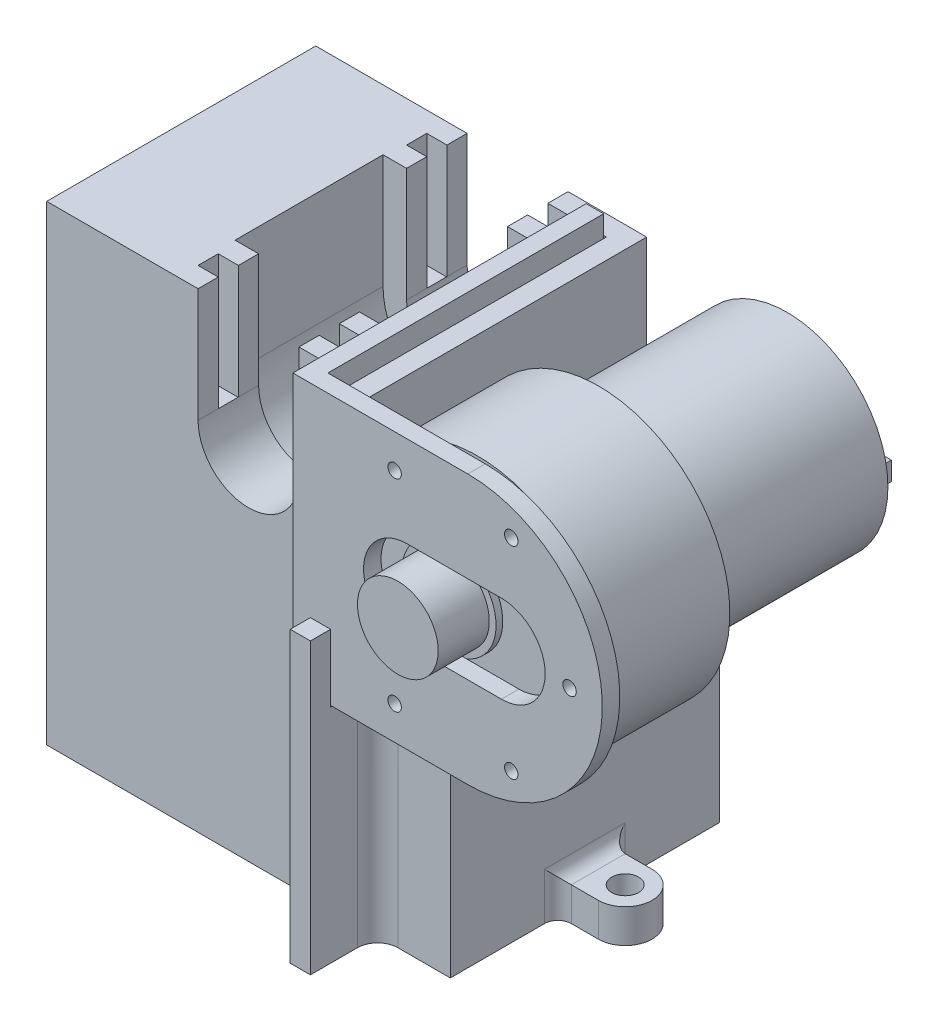
SolidWorks part; units mm, degrees
ref_plane "前视基准面" through (0, 0, 0) normal (0, 0, 1) x (1, 0, 0)
ref_plane "上视基准面" through (0, 0, 0) normal (0, 1, 0) x (1, 0, 0)
ref_plane "右视基准面" through (0, 0, 0) normal (1, 0, 0) x (0, 0, -1)
sketch "Sketch1" plane through (0, 5, 0) normal (0, 1, 0) x (1, 0, 0)
  line L1 (-150, -20) -> (-90, -20)
  line L2 (-150, -20) -> (-150, 20)
  line L3 (-150, 20) -> (-90, 20)
  line L4 (-90, -20) -> (-90, 20)
  line L5 (-150, -20) -> (-90, 20) construction
  line L6 (-150, 20) -> (-90, -20) construction
  point P0 (-120, 0)
  dimension "D1" = 40
  dimension "D2" = 60
  dimension "D3" = 120
extrude "Extrude1" add sketch "Sketch1" along normal blind 70
sketch "Sketch2" plane through (0, 0, 20) normal (0, 0, 1) x (1, 0, 0)
  circle A0 centre (-120, 58.05) radius 7.5
  circle A1 centre (-120, 58.05) radius 7.5
  point P5 (-120, 58.05)
sketch "Sketch4" plane through (0, 0, 20) normal (0, 0, 1) x (1, 0, 0)
  line L0 (-106.8, 75) -> (-106.8, 38)
  line L1 (-150, 75) -> (-90, 75) construction
  line L2 (-106.8, 38) -> (-69.3408, 38)
  line L3 (-69.3408, 38) -> (-69.3408, 101.6783)
  line L4 (-69.3408, 101.6783) -> (-106.8, 101.6783)
  line L5 (-106.8, 101.6783) -> (-106.8, 75)
  circle A0 centre (-88.8, 58.05) radius 3 construction
  point P5 (-120, 58.05)
  dimension "D1" = 31.2
  dimension "D2" = 6
  dimension "D3" = 18
  dimension "D4" = 37
extrude "Extrude2" cut sketch "Sketch4" against normal through all
sketch "Sketch5" plane through (0, 0, 20) normal (0, 0, 1) x (1, 0, 0)
  circle A0 centre (-120, 58.05) radius 7.5
  dimension "D1" = 15
extrude "Extrude3" cut sketch "Sketch5" against normal through all
sketch "Sketch7" plane through (0, 0, 20) normal (0, 0, 1) x (1, 0, 0)
  circle A0 centre (-120, 58.05) radius 11
  dimension "D1" = 22
ref_plane "Plane1" through (0, 0, 0) normal (0, 0, 1) x (1, 0, 0)
sketch "Sketch8" plane through (0, 0, 0) normal (0, 0, 1) x (1, 0, 0)
  circle A0 centre (-120, 58.05) radius 11 construction
  circle A1 centre (-120, 58.05) radius 11
extrude "Extrude5" cut sketch "Sketch8" against normal mid plane 22
sketch "Sketch9" plane through (0, 0, 20) normal (0, 0, 1) x (1, 0, 0)
  line L0 (-112.5, 75) -> (-112.5, 58.05)
  line L1 (-150, 75) -> (-106.8, 75) construction
  line L2 (-112.5, 58.05) -> (-127.5, 58.05)
  line L3 (-127.5, 58.05) -> (-127.5, 75)
  line L4 (-127.5, 75) -> (-112.5, 75)
  circle A3 centre (-120, 58.05) radius 7.5 construction
extrude "Extrude6" cut sketch "Sketch9" against normal through all
sketch "Sketch10" plane through (0, 0, 0) normal (0, 0, 1) x (1, 0, 0)
  line L0 (-109, 58.05) -> (-109, 89.3948)
  line L1 (-131, 58.05) -> (-131, 89.3948)
  line L2 (-131, 89.3948) -> (-109, 89.3948)
  line L3 (-131, 58.05) -> (-109, 58.05)
  circle A0 centre (-120, 58.05) radius 11 construction
  arc A1 (-109, 58.05) -> (-131, 58.05) centre (-120, 58.05) ccw construction
extrude "Extrude7" cut sketch "Sketch10" against normal mid plane 22
ref_plane "Plane2" through (0, 0, 27) normal (0, 0, 1) x (1, 0, 0)
ref_plane "Plane3" through (0, 0, -17) normal (0, 0, 1) x (1, 0, 0)
ref_plane "Plane4" through (0, 58, 0) normal (0, 1, 0) x (1, 0, 0)
sketch "Sketch13" plane through (-127.5, 0, 0) normal (1, 0, 0) x (0, 0, -1)
  line L0 (-20, 75) -> (20, 75) construction
  line L1 (-17, 75) -> (-14, 75)
  line L2 (-17, 75) -> (-17, 58)
  line L3 (-17, 58) -> (-14, 58)
  line L4 (-14, 75) -> (-14, 58)
  line L5 (3.135, 58) -> (-3.135, 58) construction
  line L6 (-11, 75) -> (-11, 58.05) construction
  dimension "D1" = 3
  dimension "D2" = 3
extrude "Extrude9" cut sketch "Sketch13" against normal blind 3
sketch "Sketch14" plane through (-112.5, 0, 0) normal (-1, 0, 0) x (0, 0, 1)
  line L0 (17, 75) -> (17, 58) construction
  line L1 (14, 58) -> (14, 75) construction
  line L2 (17, 58) -> (14, 58) construction
  line L3 (14, 75) -> (17, 75) construction
  line L4 (17, 75) -> (17, 58)
  line L5 (14, 58) -> (14, 75)
  line L6 (17, 58) -> (14, 58)
  line L7 (14, 75) -> (17, 75)
extrude "Extrude10" cut sketch "Sketch14" against normal blind 3
mirror "Mirror1" about plane through (0, 0, 0) normal (0, 0, 1) of "Extrude10", "Extrude9"
sketch "Sketch15" plane through (0, 0, 20) normal (0, 0, 1) x (1, 0, 0)
  line L0 (-112.5, 58.05) -> (-112.5, 75) construction
  line L1 (-127.5, 75) -> (-127.5, 58.05) construction
  line L2 (-112.5, 58.05) -> (-112.5, 75)
  line L3 (-127.5, 75) -> (-127.5, 58.05)
  line L4 (-127.5, 75) -> (-112.5, 75)
  circle A0 centre (-120, 58.05) radius 7.5 construction
  arc A1 (-112.5, 58.05) -> (-127.5, 58.05) centre (-120, 58.05) ccw
sketch "Sketch16" plane through (0, 0, -17) normal (0, 0, 1) x (1, 0, 0)
  line L0 (-106.8, 38) -> (-90, 38) construction
  line L1 (-100.8, 38) -> (-103.8, 38)
  line L2 (-100.8, 38) -> (-100.8, 75)
  line L3 (-100.8, 75) -> (-103.8, 75)
  line L4 (-103.8, 38) -> (-103.8, 75)
  line L5 (-106.8, 75) -> (-106.8, 38) construction
  line L6 (-127.5, 75) -> (-150, 75) construction
  dimension "D1" = 3
  dimension "D2" = 3
extrude "Extrude11" add sketch "Sketch16" along normal offset from surface (41 mm away) 3 up to plane "Plane2"
sketch "Sketch17" plane through (-100.8, 0, 0) normal (1, 0, 0) x (0, 0, -1)
  line L0 (17, 38) -> (17, 75) construction
  line L1 (17, 75) -> (20, 75)
  line L2 (17, 75) -> (17, 38)
  line L3 (17, 38) -> (20, 38)
  line L4 (20, 75) -> (20, 38)
  line L5 (-24, 75) -> (17, 75) construction
  line L6 (-20, 38) -> (17, 38) construction
  line L7 (20, 75) -> (20, 38) construction
extrude "Extrude12" add sketch "Sketch17" against normal up to surface (6 mm away) up to face at (-106.8, 56.5, 0)
sketch "Sketch18" plane through (0, 38, 0) normal (0, -1, 0) x (1, 0, 0)
  line L0 (-150, 20) -> (-90, 20) construction
  line L1 (-100.8, 20) -> (-103.8, 20)
  line L2 (-100.8, 20) -> (-100.8, 30)
  line L3 (-100.8, 30) -> (-103.8, 30)
  line L4 (-103.8, 20) -> (-103.8, 30)
  line L5 (-103.8, 24) -> (-103.8, 20) construction
  line L6 (33, 27) -> (-33, 27) construction
  dimension "D1" = 3
  dimension "D2" = 3
extrude "Extrude13" add sketch "Sketch18" along normal up to surface (33 mm away) up to face at (-120, 5, 0)
sketch "Sketch19" plane through (0, 38, 0) normal (0, 1, 0) x (1, 0, 0)
  line L0 (-33, -27) -> (33, -27) construction
  line L1 (-100.8, -30) -> (-103.8, -30)
  line L2 (-100.8, -30) -> (-100.8, -27)
  line L3 (-100.8, -27) -> (-103.8, -27)
  line L4 (-103.8, -30) -> (-103.8, -27)
  line L5 (-103.8, -30) -> (-103.8, -24) construction
extrude "Extrude14" add sketch "Sketch19" along normal blind 10
fillet "Fillet1" radius 3 3 edges at (-103.8, 21.5, 20) (-100.8, 21.5, 20) (-100.8, 38, 0)
sketch "Sketch20" plane through (0, 5, 0) normal (0, -1, 0) x (1, 0, 0)
  line L0 (-150, -20) -> (-150, 20) construction
  line L1 (-156, 4) -> (-150, 4)
  line L2 (-150, 4) -> (-150, -4)
  line L3 (-150, -4) -> (-156, -4)
  circle A0 centre (-156, 0) radius 2
  arc A1 (-156, 4) -> (-156, -4) centre (-156, 0) ccw
  dimension "D1" = 4
  dimension "D2" = 8
  dimension "D3" = 6
extrude "Extrude15" add sketch "Sketch20" against normal blind 5
fillet "Fillet2" radius 2 3 edges at (-150, 7.5, 4) (-150, 10, 0) (-150, 7.5, -4)
ref_plane "Plane5" through (-120, 0, 0) normal (-1, 0, 0) x (0, 0, 1)
mirror "Mirror7" about plane through (-120, 0, 0) normal (-1, 0, 0) of "Extrude15"
fillet "Fillet3" radius 2 3 edges at (-90, 7.5, -4) (-90, 10, 0) (-90, 7.5, 4)
sketch "Sketch21" plane through (0, 38, 0) normal (0, 1, 0) x (1, 0, 0)
  line L6 (-104, -21.4508) -> (-104, 16.8)
  line L7 (-104, 16.8) -> (-106.6, 16.8)
  line L8 (-106.6, 16.8) -> (-106.6, -19.8063)
  line L9 (-104, -21.4508) -> (-104, 16.8)
  line L10 (-104, 16.8) -> (-106.6, 16.8)
  line L11 (-106.6, 16.8) -> (-106.6, -19.8063)
  line L13 (-106.6, -19.8063) -> (-106.6, -26.8)
  line L14 (-106.6, -26.8) -> (-103.6, -26.8)
  line L15 (-104, -21.4508) -> (-104, -24.2)
  line L16 (-104, -24.2) -> (-103.6, -24.2)
  line L17 (-103.6, -26.8) -> (-101, -26.8)
  line L18 (-101, -26.8) -> (-101, -24.2)
  line L19 (-101, -24.2) -> (-103.6, -24.2)
  line L20 (-103.6, -24.2) -> (-103.6, -26.8)
  line L21 (-103.6, -26.8) -> (-101, -26.8)
  line L22 (-101, -26.8) -> (-60.6, -26.8)
  line L23 (-101, -24.2) -> (-103.6, -24.2)
  line L24 (-60.6, -26.8) -> (-60.6, -24.2)
  line L25 (-60.6, -24.2) -> (-101, -24.2)
  arc A2 (-104, -21.4508) -> (-106.6, -19.8063) centre (-106.8, -23) ccw
  dimension "D3" = 46
  dimension "D1" = 0.2
  dimension "D2" = 0.2
extrude "Extrude16" add sketch "Sketch21" along normal blind 40
fillet "Fillet4" 2 edges at (-60.6, 78, 25.5) (-60.6, 38, 25.5) type full round first side face at (-90.4, 78, 11.4) second side face at (-80.7, 38, 25.5) middle face at (-60.6, 58, 25.5)
sketch "Sketch22" plane through (0, 0, 26.8) normal (0, 0, 1) x (1, 0, 0)
  line L0 (-106.6, 78) -> (-106.6, 38) construction
  line L1 (-89.6, 51.5) -> (-75.6, 51.5)
  line L2 (-75.6, 64.5) -> (-89.6, 64.5)
  arc A0 (-89.6, 64.5) -> (-89.6, 51.5) centre (-89.6, 58) ccw
  arc A1 (-80.6, 38) -> (-80.6, 78) centre (-80.6, 58) ccw construction
  arc A2 (-75.6, 51.5) -> (-75.6, 64.5) centre (-75.6, 58) ccw
  point P6 (-60.6, 58)
  dimension "D1" = 13
  dimension "D2" = 17
  dimension "D4" = 14
extrude "Extrude17" cut sketch "Sketch22" against normal up to surface (2.6 mm away) up to face at (-92.3, 51.3333, 24.2)
sketch "Sketch23" plane through (0, 0, 26.8) normal (0, 0, 1) x (1, 0, 0)
  arc A0 (-75.6, 51.5) -> (-75.6, 64.5) centre (-75.6, 58) ccw construction
  point P0 (-82.1, 57.7624)
  point P4 (-69.1, 58)
  dimension "D1" = 13
sketch "Sketch24" plane through (0, 0, 26.8) normal (0, 0, 1) x (1, 0, 0)
  circle A0 centre (-65.4708, 58) radius 1
  circle A1 centre (-74.1384, 42.9873) radius 1
  circle A2 centre (-91.4735, 42.9873) radius 1
  circle A3 centre (-100.1411, 58) radius 1
  circle A4 centre (-91.4735, 73.0127) radius 1
  circle A5 centre (-74.1384, 73.0127) radius 1
  point P16 (-82.8059, 58)
  dimension "D1" = 2
  dimension "D2" = 6
extrude "Extrude18" cut sketch "Sketch24" against normal up to surface (2.6 mm away) up to face at (-82.6, 58, 24.2)
sketch "Sketch25" plane through (0, 0, 26.8) normal (0, 0, 1) x (1, 0, 0)
  circle A0 centre (-100.1411, 58) radius 2.5
extrude "Extrude19" add sketch "Sketch25" against normal up to surface (2.6 mm away) up to face at (-73.1384, 42.9873, 24.2)
sketch "Sketch26" plane through (0, 0, 26.8) normal (0, 0, 1) x (1, 0, 0)
  circle A0 centre (-86, 58) radius 6
  arc A1 (-89.6, 64.5) -> (-89.6, 51.5) centre (-89.6, 58) ccw construction
  point P5 (-96.1, 58)
  dimension "D1" = 10.1
  dimension "D2" = 12
extrude "Extrude20" add sketch "Sketch26" along normal blind 5 separate body
sketch "Sketch27" plane through (0, 0, 26.8) normal (0, 0, -1) x (-1, 0, 0)
  circle A1 centre (86, 58) radius 6
  circle A2 centre (86, 58) radius 6
  dimension "D1" = 0
extrude "Extrude21" add sketch "Sketch27" along normal up to surface (2.6 mm away) up to face at (-73.1384, 42.9873, 24.2)
sketch "Sketch28" plane through (0, 0, 24.2) normal (0, 0, -1) x (-1, 0, 0)
  circle A2 centre (86, 58) radius 7
  circle A3 centre (86, 58) radius 7
  dimension "D1" = 1
extrude "Extrude22" add sketch "Sketch28" along normal blind 1
sketch "Sketch29" plane through (0, 0, 23.2) normal (0, 0, -1) x (-1, 0, 0)
  circle A0 centre (82.7367, 57.9529) radius 19.5
  dimension "D1" = 39
extrude "Extrude23" add sketch "Sketch29" along normal blind 18
sketch "Sketch30" plane through (0, 0, 5.2) normal (0, 0, -1) x (-1, 0, 0)
  circle A0 centre (82.7367, 57.9529) radius 15
  dimension "D1" = 30
extrude "Extrude24" add sketch "Sketch30" along normal blind 28
sketch "Sketch31" plane through (0, 0, -22.8) normal (0, 0, -1) x (-1, 0, 0)
  line L1 (70.2407, 58.6664) -> (71.2933, 58.6664)
  line L2 (70.2407, 58.6664) -> (70.2407, 55.8854)
  line L3 (70.2407, 55.8854) -> (71.2933, 55.8854)
  line L4 (71.2933, 58.6664) -> (71.2933, 55.8854)
  line L5 (95.8917, 55.8854) -> (94.6651, 55.8854)
  line L6 (95.8917, 55.8854) -> (95.8917, 58.6664)
  line L7 (95.8917, 58.6664) -> (94.6651, 58.6664)
  line L8 (94.6651, 55.8854) -> (94.6651, 58.6664)
extrude "Extrude25" add sketch "Sketch31" along normal blind 3
